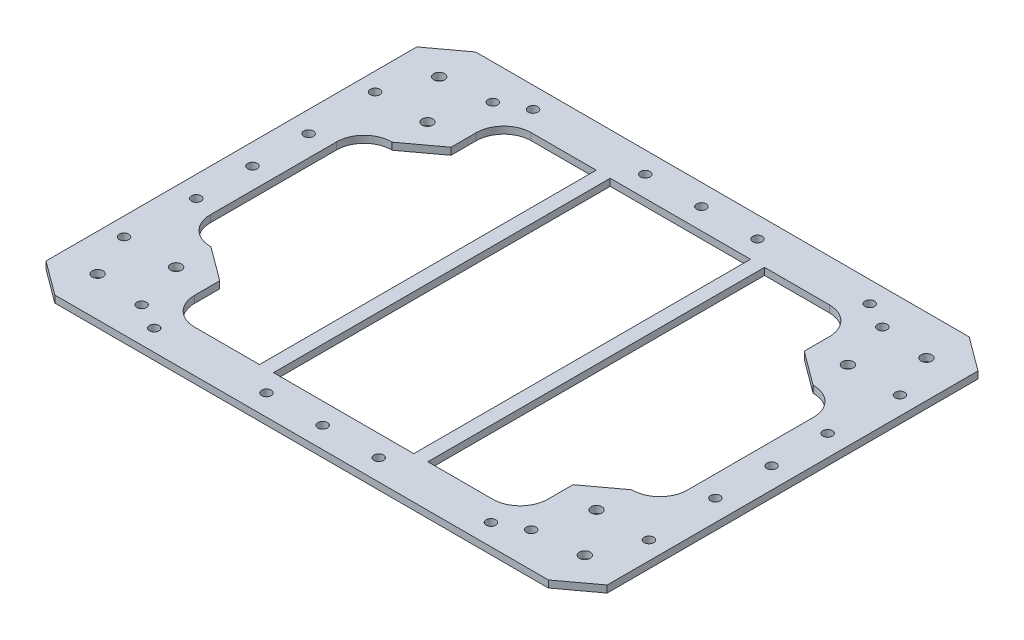
SolidWorks part; units mm, degrees
material "Thornel Mat VMA"
ref_plane "Front Plane" through (0, 0, 0) normal (0, 0, 1) x (1, 0, 0)
ref_plane "Top Plane" through (0, 0, 0) normal (0, 1, 0) x (1, 0, 0)
ref_plane "Right Plane" through (0, 0, 0) normal (1, 0, 0) x (0, 0, -1)
sketch "Sketch1" plane through (0, 0, 0) normal (0, 1, 0) x (1, 0, 0)
  line L0 (-127, 83.9186) -> (-111.6865, 95.25)
  line L1 (-127, -95.25) -> (127, -95.25)
  line L2 (-127, -95.25) -> (-127, 95.25)
  line L3 (-127, 95.25) -> (127, 95.25)
  line L4 (127, -95.25) -> (127, 95.25)
  line L5 (-107.95, 28.565) -> (-107.95, -28.565)
  line L7 (-38.1, -76.2) -> (-38.1, 76.2)
  line L8 (-95.504, 41.011) -> (-95.25, 41.011)
  line L9 (-31.75, -76.2) -> (-31.75, 76.2)
  line L10 (-127, 95.25) -> (127, -95.25) construction
  line L12 (127, 83.9186) -> (111.6865, 95.25)
  line L13 (38.1, -76.2) -> (38.1, 76.2)
  line L14 (79.9365, 52.3423) -> (79.9365, 63.754)
  line L15 (95.25, 41.011) -> (79.9365, 52.3423)
  line L16 (95.504, 41.011) -> (95.25, 41.011)
  line L17 (107.95, 28.565) -> (107.95, -28.565)
  line L18 (127, -83.9186) -> (111.6865, -95.25)
  line L19 (95.504, -41.011) -> (95.25, -41.011)
  line L20 (95.25, -41.011) -> (79.9365, -52.3423)
  line L21 (79.9365, -52.3423) -> (79.9365, -63.754)
  line L22 (127, 0) -> (-127, 0) construction
  line L23 (0, -13.6985) -> (0, 95.25) construction
  line L25 (-67.4905, -76.2) -> (-38.1, -76.2)
  line L26 (-79.9365, -52.3423) -> (-79.9365, -63.754)
  line L27 (-95.25, 41.011) -> (-127, 83.9186) construction
  line L28 (-95.25, 41.011) -> (-79.9365, 52.3423)
  line L29 (-79.9365, 52.3423) -> (-79.9365, 63.754)
  line L30 (-67.4905, 76.2) -> (-38.1, 76.2)
  line L31 (-95.25, -41.011) -> (-79.9365, -52.3423)
  line L32 (-95.504, -41.011) -> (-95.25, -41.011)
  line L33 (-127, -83.9186) -> (-111.6865, -95.25)
  line L34 (-79.9365, 52.3423) -> (-111.6865, 95.25) construction
  line L35 (31.75, -76.2) -> (31.75, 76.2)
  line L36 (-31.75, 76.2) -> (31.75, 76.2)
  line L37 (38.1, 76.2) -> (67.4905, 76.2)
  line L38 (-31.75, -76.2) -> (31.75, -76.2)
  line L39 (38.1, -76.2) -> (67.4905, -76.2)
  arc A0 (-79.9365, 63.754) -> (-67.4905, 76.2) centre (-67.4905, 63.754) cw
  arc A1 (79.9365, 63.754) -> (67.4905, 76.2) centre (67.4905, 63.754) ccw
  arc A2 (79.9365, -63.754) -> (67.4905, -76.2) centre (67.4905, -63.754) cw
  arc A3 (-67.4905, -76.2) -> (-79.9365, -63.754) centre (-67.4905, -63.754) cw
  arc A4 (-95.504, -41.011) -> (-107.95, -28.565) centre (-95.504, -28.565) cw
  arc A5 (-107.95, 28.565) -> (-95.504, 41.011) centre (-95.504, 28.565) cw
  arc A6 (95.504, 41.011) -> (107.95, 28.565) centre (95.504, 28.565) cw
  arc A7 (95.504, -41.011) -> (107.95, -28.565) centre (95.504, -28.565) ccw
  point P0 (0, 0)
  point P1 (0, 0)
  point P14 (0, 0)
  point P22 (0, 76.2)
  point P33 (107.95, 0)
  point P41 (0, 0)
  point P44 (-107.95, 0)
  point P45 (-38.1, 0)
  point P46 (-31.75, 0)
  dimension "D10" = 12.446
  dimension "D1" = 190.5
  dimension "D2" = 254
  dimension "D3" = 19.05
  dimension "D4" = 19.05
  dimension "D9" = 31.75
  dimension "D5" = 143.5
  dimension "D6" = 19.05
  dimension "D8" = 6.35
extrude "Boss-Extrude1" add sketch "Sketch1" along normal blind 3.175 contours L2 L1 L4 L3 L8 region at (-117.4547, 0, -87.0321)
sketch "Sketch2" plane through (0, 3.175, 0) normal (0, 1, 0) x (1, 0, 0)
  line L0 (-87.5933, 46.6767) -> (-119.3433, 89.5843) construction
  line L1 (-95.25, 41.011) -> (-79.9365, 52.3423) construction
  line L2 (-127, 83.9186) -> (-111.6865, 95.25) construction
  line L3 (0, 0) -> (0, 95.25) construction
  line L4 (-111.6865, 95.25) -> (111.6865, 95.25) construction
  line L5 (0, 0) -> (-127, 0) construction
  line L6 (-127, -83.9186) -> (-127, 83.9186) construction
  line L7 (-103.4683, 68.1305) -> (-88.1548, 79.4619) construction
  circle A0 centre (-95.1475, 56.8856) radius 2.4638
  circle A1 centre (-110.256, 77.3036) radius 2.4638
  circle A2 centre (110.256, 77.3036) radius 2.4638
  circle A3 centre (95.1475, 56.8856) radius 2.4638
  circle A4 centre (110.256, -77.3036) radius 2.4638
  circle A5 centre (95.1475, -56.8856) radius 2.4638
  circle A6 centre (-110.256, -77.3036) radius 2.4638
  circle A7 centre (-95.1475, -56.8856) radius 2.4638
  circle A8 centre (-88.1548, 79.4619) radius 2.159
  circle A9 centre (-118.7817, 56.7991) radius 2.159
  circle A10 centre (118.7817, 56.7991) radius 2.159
  circle A11 centre (88.1548, 79.4619) radius 2.159
  circle A12 centre (118.7817, -56.7991) radius 2.159
  circle A13 centre (88.1548, -79.4619) radius 2.159
  circle A14 centre (-88.1548, -79.4619) radius 2.159
  circle A15 centre (-118.7817, -56.7991) radius 2.159
  dimension "D2" = 4.9276
  dimension "D3" = 4.9276
  dimension "D5" = 4.318
  dimension "D1" = 25.4
  dimension "D4" = 12.7
  dimension "D6" = 19.05
extrude "Cut-Extrude1" cut sketch "Sketch2" against normal through all
sketch "Sketch3" plane through (0, 3.175, 0) normal (0, 1, 0) x (1, 0, 0)
  line L0 (-79.9365, 76.2) -> (-79.9365, 95.25) construction
  line L1 (-111.6865, 95.25) -> (111.6865, 95.25) construction
  line L2 (-79.9365, 85.725) -> (79.9365, 85.725) construction
  line L3 (79.9365, 76.2) -> (79.9365, 95.25) construction
  line L4 (0, 0) -> (76.2, 0) construction
  line L5 (-107.95, -41.011) -> (-127, -41.011) construction
  line L6 (-127, -83.9186) -> (-127, 83.9186) construction
  line L7 (-107.95, 41.011) -> (-127, 41.011) construction
  line L8 (-117.475, 41.011) -> (-117.475, -41.011) construction
  line L9 (0, 0) -> (0, 36.2879) construction
  line L11 (127, -83.9186) -> (127, 83.9186) construction
  circle A0 centre (-76.2, 85.725) radius 2.159
  circle A1 centre (-25.4, 85.725) radius 2.159
  circle A2 centre (25.4, 85.725) radius 2.159
  circle A3 centre (76.2, 85.725) radius 2.159
  circle A4 centre (76.2, -85.725) radius 2.159
  circle A5 centre (25.4, -85.725) radius 2.159
  circle A6 centre (-25.4, -85.725) radius 2.159
  circle A7 centre (-76.2, -85.725) radius 2.159
  circle A8 centre (-117.475, -25.4) radius 2.159
  circle A9 centre (-117.475, 25.4) radius 2.159
  circle A10 centre (117.475, 25.4) radius 2.159
  circle A11 centre (117.475, -25.4) radius 2.159
  circle A12 centre (0, 85.725) radius 2.159
  circle A13 centre (0, -85.725) radius 2.159
  circle A14 centre (-117.475, 0) radius 2.159
  circle A15 centre (117.475, 0) radius 2.159
  point P2 (0, 0)
  point P9 (0, 0)
  point P12 (0, 85.725)
  point P32 (0, 0)
  point P40 (-117.475, 0)
  point P59 (94.0681, -72.8352)
  dimension "D1" = 4.318
  dimension "D2" = 76.2
  dimension "D4" = 4.318
  dimension "D5" = 25.4
  dimension "D7" = 85.725
  dimension "D8" = 127
  dimension "D9" = 127
  dimension "D3" = 4
  dimension "D6" = 2
extrude "Cut-Extrude2" cut sketch "Sketch3" against normal through all
sketch "Sketch4" plane through (0, 3.175, 0) normal (0, 1, 0) x (1, 0, 0)
  line L0 (-95.1475, -56.8856) -> (-110.256, -74.8398) construction
